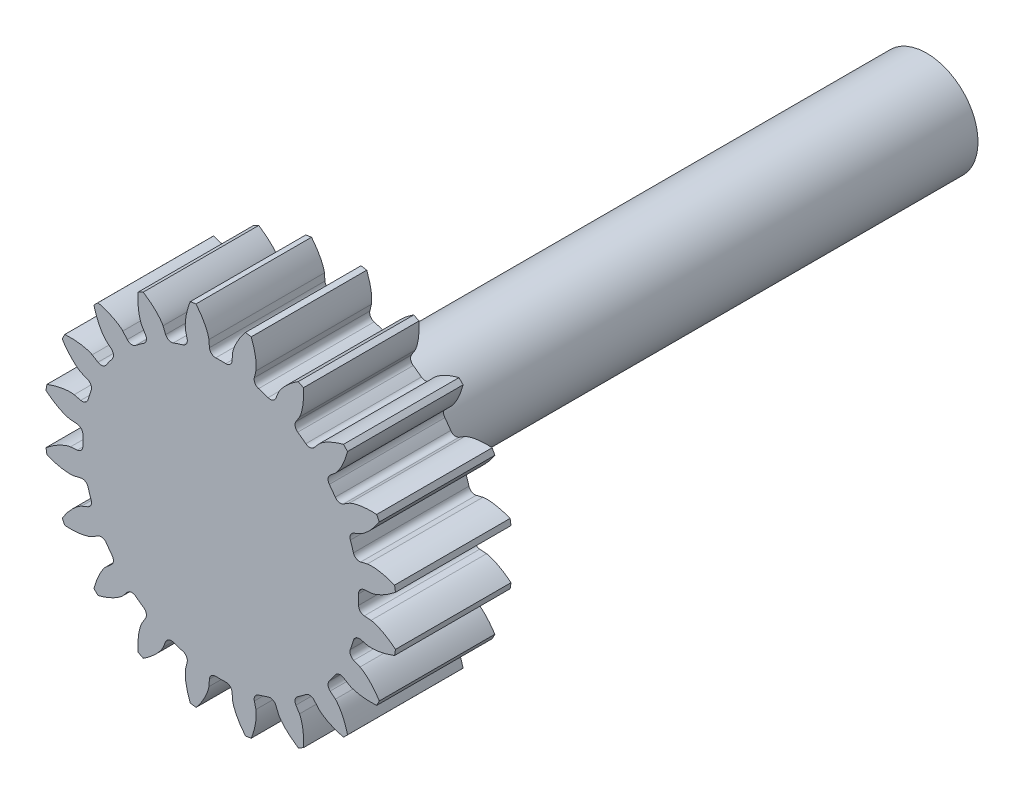
SolidWorks part; units mm, degrees
ref_plane "Front Plane" through (0, 0, 0) normal (0, 0, 1) x (1, 0, 0)
ref_plane "Top Plane" through (0, 0, 0) normal (0, 1, 0) x (1, 0, 0)
ref_plane "Right Plane" through (0, 0, 0) normal (1, 0, 0) x (0, 0, -1)
ref_axis "Gear Axis" through (0, 0, -0.4501) along (0, 0, 1)
sketch "Blank Sketch" plane through (0, 0, 0) normal (0, 0, 1) x (1, 0, 0)
  circle A0 centre (0, 0) radius 13.75
  dimension "OD" = 27.5
extrude "Blank" add sketch "Blank Sketch" along normal blind 9
sketch "Tooth Space Sketch" plane through (0, 0, 0) normal (0, 0, 1) x (1, 0, 0)
  line L0 (11.7099, 0.9227) -> (11.1803, 0.881)
  line L1 (11.7099, -0.9227) -> (11.1803, -0.881)
  line L2 (14.6961, 3.0042) -> (14.6961, -3.0042)
  arc A0 (11.1803, 0.881) -> (10.7429, 0.3902) centre (11.2176, 0.4075) ccw
  arc A1 (10.7429, -0.3902) -> (11.1803, -0.881) centre (11.2176, -0.4075) ccw
  arc A2 (10.7429, -0.3902) -> (10.7429, 0.3902) centre (0, 0) ccw
  spline S0 degree 4 poles (11.7099, 0.9227) (11.7153, 0.9232) (11.7306, 0.925) (11.7593, 0.9294) (11.806, 0.9382) (11.8651, 0.9517) (11.9409, 0.9719) (12.0295, 0.999) (12.1261, 1.0323) (12.2301, 1.0723) (12.3329, 1.1155) (12.4344, 1.1617) (12.5347, 1.2105) (12.6549, 1.2727) (12.7975, 1.3519) (12.9615, 1.4507) (13.1443, 1.5703) (13.3269, 1.7) (13.5034, 1.834) (13.678, 1.9766) (13.8441, 2.1196) (14.0125, 2.2754) (14.1658, 2.4228) (14.3326, 2.5956) (14.4659, 2.7374) (14.6362, 2.9324) (14.7351, 3.0499) (14.8489, 3.1902) (14.8984, 3.2539) (14.9289, 3.293) knots 0 0 0 0 0 0.005377 0.015084 0.028532 0.04661 0.064855 0.092111 0.119476 0.146842 0.174209 0.201575 0.228941 0.256307 0.307035 0.361767 0.4165 0.471232 0.525964 0.580697 0.635429 0.690161 0.744894 0.799626 0.854358 0.909091 0.954545 1 1 1 1 1 construction
  spline S1 degree 4 poles (11.7099, 0.9227) (11.7153, 0.9232) (11.7306, 0.925) (11.7593, 0.9294) (11.806, 0.9382) (11.8651, 0.9517) (11.9409, 0.9719) (12.0295, 0.999) (12.1261, 1.0323) (12.2301, 1.0723) (12.3329, 1.1155) (12.4344, 1.1617) (12.5347, 1.2105) (12.6549, 1.2727) (12.7975, 1.3519) (12.9615, 1.4507) (13.1443, 1.5703) (13.3269, 1.7) (13.5034, 1.834) (13.678, 1.9766) (13.8441, 2.1196) (14.0125, 2.2754) (14.1658, 2.4228) (14.3326, 2.5956) (14.4659, 2.7374) (14.5992, 2.8901) (14.6635, 2.9654) (14.6961, 3.0042) knots 0 0 0 0 0 0.005377 0.015084 0.028532 0.04661 0.064855 0.092111 0.119476 0.146842 0.174209 0.201575 0.228941 0.256307 0.307035 0.361767 0.4165 0.471232 0.525964 0.580697 0.635429 0.690161 0.744894 0.799626 0.854358 0.909091 0.909091 0.909091 0.909091 0.909091
  spline S2 degree 4 poles (11.7099, -0.9227) (11.7153, -0.9232) (11.7306, -0.925) (11.7593, -0.9294) (11.806, -0.9382) (11.8651, -0.9517) (11.9409, -0.9719) (12.0295, -0.999) (12.1261, -1.0323) (12.2301, -1.0723) (12.3329, -1.1155) (12.4344, -1.1617) (12.5347, -1.2105) (12.6549, -1.2727) (12.7975, -1.3519) (12.9615, -1.4507) (13.1443, -1.5703) (13.3269, -1.7) (13.5034, -1.834) (13.678, -1.9766) (13.8441, -2.1196) (14.0125, -2.2754) (14.1658, -2.4228) (14.3326, -2.5956) (14.4659, -2.7374) (14.6362, -2.9324) (14.7351, -3.0499) (14.8489, -3.1902) (14.8984, -3.2539) (14.9289, -3.293) knots 0 0 0 0 0 0.005377 0.015084 0.028532 0.04661 0.064855 0.092111 0.119476 0.146842 0.174209 0.201575 0.228941 0.256307 0.307035 0.361767 0.4165 0.471232 0.525964 0.580697 0.635429 0.690161 0.744894 0.799626 0.854358 0.909091 0.954545 1 1 1 1 1 construction
  spline S3 degree 4 poles (11.7099, -0.9227) (11.7153, -0.9232) (11.7306, -0.925) (11.7593, -0.9294) (11.806, -0.9382) (11.8651, -0.9517) (11.9409, -0.9719) (12.0295, -0.999) (12.1261, -1.0323) (12.2301, -1.0723) (12.3329, -1.1155) (12.4344, -1.1617) (12.5347, -1.2105) (12.6549, -1.2727) (12.7975, -1.3519) (12.9615, -1.4507) (13.1443, -1.5703) (13.3269, -1.7) (13.5034, -1.834) (13.678, -1.9766) (13.8441, -2.1196) (14.0125, -2.2754) (14.1658, -2.4228) (14.3326, -2.5956) (14.4659, -2.7374) (14.5992, -2.8901) (14.6635, -2.9654) (14.6961, -3.0042) knots 0 0 0 0 0 0.005377 0.015084 0.028532 0.04661 0.064855 0.092111 0.119476 0.146842 0.174209 0.201575 0.228941 0.256307 0.307035 0.361767 0.4165 0.471232 0.525964 0.580697 0.635429 0.690161 0.744894 0.799626 0.854358 0.909091 0.909091 0.909091 0.909091 0.909091
  dimension "Root" = 10.75
  dimension "Fillet" = 0.475
extrude "Tooth Space" cut sketch "Tooth Space Sketch" against normal through all both and the other way through all both
pattern_circular "Teeth" count 20 over 360 about axis through (0, 0, -0.4501) along (0, 0, 1) of "Tooth Space"
sketch "Bore Sketch" plane through (0, 0, 0) normal (0, 0, 1) x (1, 0, 0)
  circle A0 centre (0, 0) radius 4
  dimension "Bore" = 8
extrude "Bore" cut sketch "Bore Sketch" against normal through all both and the other way through all both
sketch "Sketch1" plane through (0, 0, 9) normal (0, 0, 1) x (1, 0, 0)
  circle A0 centre (0, 0) radius 4 construction
  circle A1 centre (0, 0) radius 4
extrude "Boss-Extrude1" add sketch "Sketch1" against normal blind 55
equation "\"No. of Teeth\"= 20"
equation "\"Module\"= 1.25"
equation "\"Bore Diameter\"= 8"
equation "\"Pressure Angle\"= 20"
equation "\"Outer Diameter\"= ( \"No. of Teeth\" + 2 ) * \"Module\""
equation "\"Pitch Diameter\"= \"No. of Teeth\" * \"Module\""
equation "\"Backlash\"= 0.3 * \"Module\""
equation "\"Arc Length\"= ( ( \"Module\" * pi ) / 2 + \"Backlash\" )"
equation "\"Fillet Radius\"= 0.38 * \"Module\""
equation "\"Tooth Depth\"= IIF ( \"Module\" <= 1.25 , \"Module\" * 2.4 , \"Module\" * 2.25 )"
equation "\"Face Width\"= 9"
equation "\"Root Diameter\"= \"Outer Diameter\" - 2 * \"Tooth Depth\""
equation "\"Base Diameter\"= \"Pitch Diameter\" * cos ( \"Pressure Angle\" )"
equation "\"Base Radius\"= \"Base Diameter\" / 2"
equation "\"Tooth Thickness\"= \"Module\" * pi - \"Arc Length\""
equation "\"Half Space Angle\"= ( \"Arc Length\" / \"Pitch Diameter\" ) * 180 / pi"
equation "\"Involute Fn\"= tan ( \"Pressure Angle\" ) - \"Pressure Angle\" * pi / 180"
equation "\"Flank Offset\"= \"Arc Length\" / \"Pitch Diameter\" - \"Involute Fn\""
equation "\"Tip Cap Diameter\"= \"Outer Diameter\" + 2 * \"Module\""
equation "\"Flank Start Diameter\"= IIF ( \"Base Diameter\" >= ( \"Root Diameter\" + 3 * \"Fillet Radius\" ) , \"Base Diameter\" , \"Root Diameter\" + 3 * \"Fillet Radius\" )"
equation "\"Involute t1\"= ( abs ( ( \"Flank Start Diameter\" / \"Base Diameter\" ) ^ 2 - 1 ) ) ^ 0.5"
equation "\"Involute t2\"= ( abs ( ( \"Tip Cap Diameter\" / \"Base Diameter\" ) ^ 2 - 1 ) ) ^ 0.5"
equation "\"Flank Arc Radius\"= ( \"Pitch Diameter\" / 2 ) * sin ( \"Pressure Angle\" )"
equation "\"Flank Centre Angle\"= \"Half Space Angle\" + \"Pressure Angle\""
equation "\"OD@Blank Sketch\"= \"Outer Diameter\""
equation "\"Width@Blank\"= \"Face Width\""
equation "\"Root@Tooth Space Sketch\"= \"Root Diameter\" / 2"
equation "\"Fillet@Tooth Space Sketch\"= \"Fillet Radius\""
equation "\"Count@Teeth\"= \"No. of Teeth\""
equation "\"Bore@Bore Sketch\"= \"Bore Diameter\""
